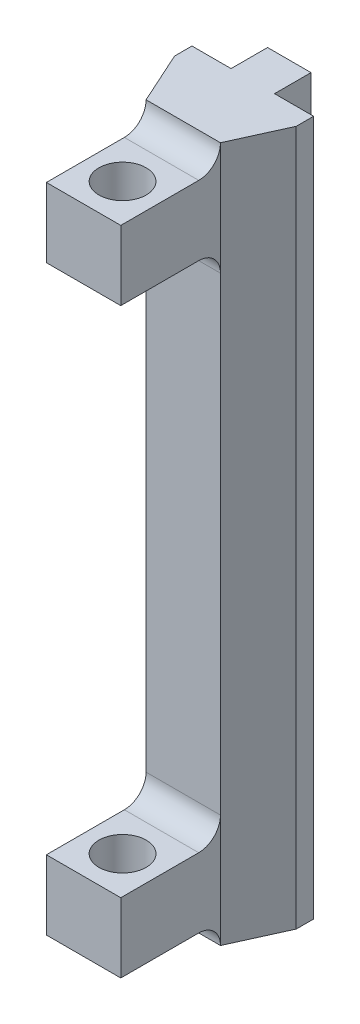
SolidWorks part; units mm, degrees
ref_plane "Front Plane" through (0, 0, 0) normal (0, 0, 1) x (1, 0, 0)
ref_plane "Top Plane" through (0, 0, 0) normal (0, 1, 0) x (1, 0, 0)
ref_plane "Right Plane" through (0, 0, 0) normal (1, 0, 0) x (0, 0, -1)
sketch "Sketch1" plane through (0, 0, 0) normal (0, 1, 0) x (1, 0, 0)
  line L0 (-4.445, 0.635) -> (4.445, -0.635) construction
  line L1 (-4.445, 0.635) -> (4.445, 0.635)
  line L2 (-4.445, 0.635) -> (-4.445, -0.635)
  line L3 (-4.445, -0.635) -> (4.445, -0.635) construction
  line L4 (4.445, 0.635) -> (4.445, -0.635)
  line L5 (-4.445, -0.635) -> (-2.7178, -4.445)
  line L6 (-2.7178, -4.445) -> (2.7178, -4.445)
  line L7 (2.7178, -4.445) -> (4.445, -0.635)
  line L8 (0, -4.445) -> (0, -0.635) construction
  point P4 (0, 0)
  point P6 (-2.7178, -3.5983)
  dimension "D1" = 8.89
  dimension "D2" = 5.08
  dimension "D3" = 5.4356
  dimension "D4" = 1.27
extrude "Boss-Extrude1" add sketch "Sketch1" against normal blind 50.8
sketch "Sketch3" plane through (0, 0, 0) normal (0, 1, 0) x (1, 0, 0)
  line L0 (4.445, 0.635) -> (-4.445, 0.635) construction
  line L1 (-1.5875, 3.302) -> (1.5875, 3.302)
  line L2 (-1.5875, 3.302) -> (-1.5875, 0.635)
  line L3 (-1.5875, 0.635) -> (1.5875, 0.635)
  line L4 (1.5875, 3.302) -> (1.5875, 0.635)
  point P6 (0, 0.635)
  dimension "D1" = 3.175
  dimension "D2" = 2.667
extrude "Boss-Extrude2" add sketch "Sketch3" against normal up to surface (50.8 mm away) up to face at (0, -50.8, 1.4817)
ref_plane "Plane2" through (0, -1.5875, 0) normal (0, 1, 0) x (1, 0, 0)
sketch "Sketch4" plane through (0, -1.5875, 0) normal (0, 1, 0) x (1, 0, 0)
  line L0 (-2.7178, -4.445) -> (2.7178, -4.445) construction
  line L1 (-2.7178, -11.729) -> (2.7178, -11.729)
  line L2 (-2.7178, -11.729) -> (-2.7178, -4.445)
  line L3 (-2.7178, -4.445) -> (2.7178, -4.445)
  line L4 (2.7178, -11.729) -> (2.7178, -4.445)
  point P6 (0, -4.445)
  point P7 (0, 0)
  dimension "D1" = 7.284
extrude "Boss-Extrude3" add sketch "Sketch4" against normal blind 5.08
fillet "Fillet1" radius 1.5875 2 edges at (0, -6.6675, 4.445) (0, -1.5875, 4.445)
hole_wizard "#4 Clearance Hole1" positions "Sketch5" profile "Sketch6" hole size "#4" standard "ANSI Inch" end condition through all
sketch "Sketch5" plane through (0, 0, 0) normal (0, 1, 0) x (1, 0, 0)
  line L0 (0, -11.729) -> (0, -6.0325) construction
  line L1 (-2.7178, -11.729) -> (2.7178, -11.729) construction
  line L3 (-2.7178, -6.0325) -> (2.7178, -6.0325) construction
  point P0 (0, -8.8807)
  point P10 (0, 0)
  point P13 (0, 0)
sketch "Sketch6" plane through (0, 0, 8.8807) normal (1, 0, 0) x (0, 0, 1)
  line L0 (0, 0) -> (0, 50.8)
  line L1 (0, 50.8) -> (1.7272, 50.8)
  line L2 (1.7272, 50.8) -> (1.7272, 0)
  line L5 (1.7272, 0) -> (0, 0)
  line L11 (0, -6.35) -> (0, 107.95) construction
  dimension "Thru Hole Dia." = 3.4544
  dimension "Thru Hole Depth" = 50.8
ref_plane "midplane" through (0, -25.4, 0) normal (0, 1, 0) x (1, 0, 0)
mirror "Mirror5" about plane through (0, -25.4, 0) normal (0, 1, 0) of "Boss-Extrude3", "Fillet1", "#4 Clearance Hole1"
